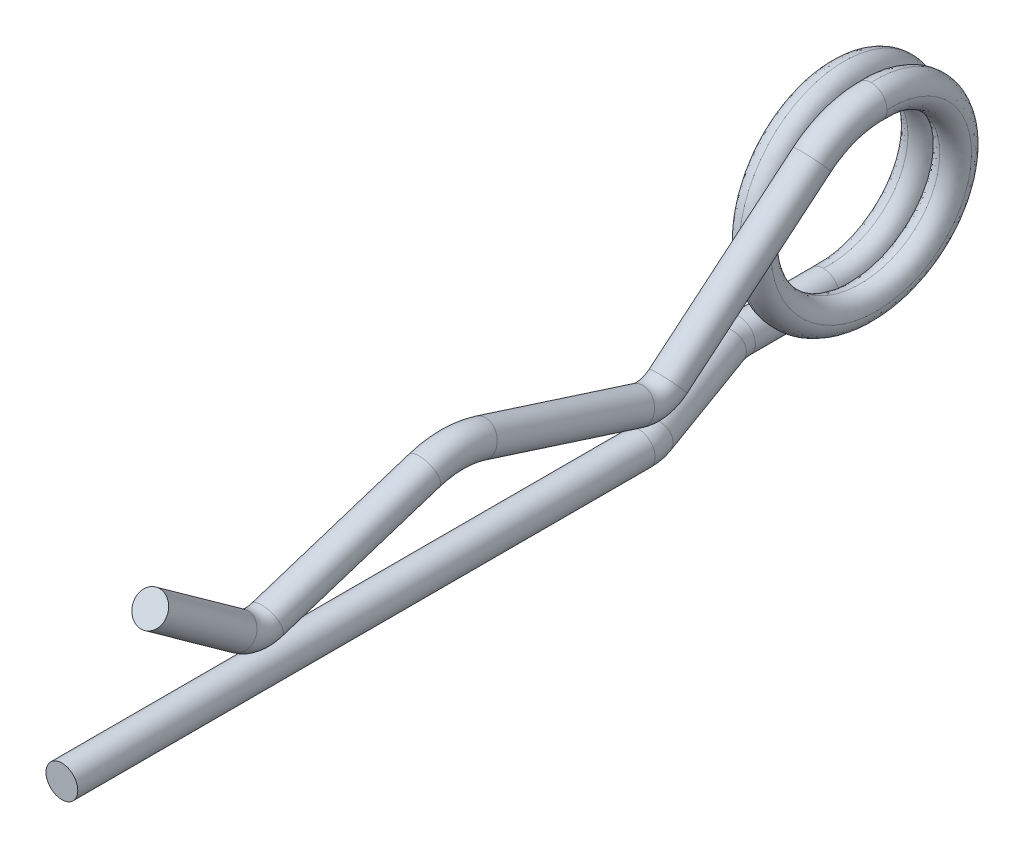
SolidWorks part; units mm, degrees
ref_plane "Front" through (0, 0, 0) normal (0, 0, 1) x (1, 0, 0)
ref_plane "Top" through (0, 0, 0) normal (0, 1, 0) x (1, 0, 0)
ref_plane "Right" through (0, 0, 0) normal (1, 0, 0) x (0, 0, -1)
sketch "Sketch1" plane through (0, 0, 0) normal (0, 0, 1) x (1, 0, 0)
  circle A0 centre (0, 0) radius 0.9906
  dimension "WireOD" = 1.9812
sketch "Sketch2" plane through (0, 0, 0) normal (0, 1, 0) x (1, 0, 0)
  line L0 (0, 0) -> (0, 35.9642)
  line L1 (-0.1792, 36.9807) -> (-2.7926, 44.1608)
  line L2 (-2.9718, 45.1772) -> (-2.9718, 50.4063)
  line L3 (-2.9718, 50.4063) -> (0, 50.4063) construction
  line L4 (0, 45.6438) -> (0, 55.1688) construction
  line L5 (0, 55.1688) -> (0, 57.15) construction
  line L6 (0, 45.6438) -> (0, 43.6626) construction
  line L7 (0, 44.6532) -> (-2.9718, 44.6532) construction
  arc A0 (-2.7926, 44.1608) -> (-2.9718, 45.1772) centre (0, 45.1772) cw
  arc A1 (0, 35.9642) -> (-0.1792, 36.9807) centre (-2.9718, 35.9642) ccw
  point P16 (0, 36.4882)
  dimension "D5" = 2.9718
  dimension "D1" = 2.9718
  dimension "EyeID" = 9.525
  dimension "D2" = 1.9812
  dimension "Length" = 57.15
  dimension "D4" = 20
sketch "Sketch3" plane through (0, 0, 0) normal (1, 0, 0) x (0, 0, -1)
  line L1 (50.4063, 0) -> (50.4063, 5.7531) construction
  line L2 (45.6438, 0) -> (55.1688, 0) construction
  line L3 (44.6532, 0) -> (44.6532, 5.7531) construction
  line L4 (45.6438, 0) -> (43.6626, 0) construction
  line L5 (50.4063, 5.7531) -> (44.6532, 5.7531) construction
  circle A0 centre (50.4063, 5.7531) radius 5.7531
curve "Helix/Spiral1" pitch 1.9812 height 2.9718 radius 5.7531 centre (0, 5.7531, -50.4063) axis (-1, 0, 0) start towards (0, 1, 0)
sketch "Sketch4" plane through (0, 0, 0) normal (1, 0, 0) x (0, 0, -1)
  line L0 (50.4063, 5.7531) -> (50.4063, 11.5062) construction
  line L1 (46.7215, 10.1713) -> (37.7572, 2.6949)
  line L2 (36.4882, 0) -> (36.4882, 2.2352) construction
  line L3 (12.1627, 0) -> (12.1627, 2.2352) construction
  line L4 (0, 0) -> (35.9642, 0) construction
  line L5 (36.4882, 0) -> (24.3255, 0) construction
  line L6 (11.0074, 2.607) -> (5.5037, 6.5578)
  line L7 (4.926, 5.7531) -> (6.0814, 7.3625) construction
  line L8 (45.6438, 0) -> (43.6626, 0) construction
  line L9 (44.6532, 5.7531) -> (4.926, 5.7531) construction
  line L10 (12.1627, 1.1176) -> (36.4882, 1.1176) construction
  line L11 (24.3255, 0) -> (24.3255, 5.7531) construction
  line L12 (35.8823, 2.3301) -> (26.0851, 5.4774)
  line L13 (22.5659, 5.4774) -> (12.7687, 2.3301)
  line L14 (6.0814, 0) -> (6.0814, 7.3625) construction
  line L15 (24.3255, 0) -> (12.1627, 0) construction
  line L16 (12.1627, 0) -> (0, 0) construction
  line L17 (0, 0.9906) -> (0, -0.9906) construction
  line L18 (0, 0) -> (0, 11.5062) construction
  line L19 (0, 11.5062) -> (57.15, 11.5062) construction
  line L20 (57.15, 11.5062) -> (57.15, 0) construction
  line L21 (55.1688, 0) -> (57.15, 0) construction
  line L22 (45.6438, 0) -> (45.6438, 5.7531) construction
  line L23 (45.6438, 5.7531) -> (55.1688, 5.7531) construction
  line L24 (24.3255, 4.6355) -> (24.3255, 6.8707) construction
  circle A0 centre (50.4063, 5.7531) radius 5.7531 construction
  arc A1 (50.4063, 11.5062) -> (46.7215, 10.1713) centre (50.4063, 5.7531) ccw
  arc A2 (35.8823, 2.3301) -> (37.7572, 2.6949) centre (36.4882, 4.2164) ccw
  arc A3 (11.0074, 2.607) -> (12.7687, 2.3301) centre (12.1627, 4.2164) ccw
  arc A4 (26.0851, 5.4774) -> (22.5659, 5.4774) centre (24.3255, 0) ccw
  circle A5 centre (24.3255, 2.8766) radius 1.759 construction
  point P46 (24.3255, 5.7531)
  point P50 (24.3255, 2.8766)
  dimension "D2" = 3.9624
  dimension "D1" = 2.2352
sweep "Sweep1" add profiles "Sketch1" path "Sketch2"
sketch "Sketch5" plane through (0, 0, -50.4063) normal (0, 0, -1) x (-1, 0, 0)
  circle A1 centre (2.9718, 0) radius 0.9906
  circle A2 centre (2.9718, 0) radius 0.9906
  dimension "D1" = 0
sweep "Sweep2" add profiles "Sketch5" path "Helix/Spiral1"
sketch "Sketch6" plane through (0, 0, -50.4063) normal (0, 0, 1) x (1, 0, 0)
  arc A4 (0.9906, 11.5062) -> (0, 12.4968) centre (0, 11.5062) ccw
  arc A5 (0, 12.4968) -> (-0.9906, 11.5062) centre (0, 11.5062) ccw
  arc A6 (-0.9906, 11.5062) -> (0, 10.5156) centre (0, 11.5062) ccw
  arc A7 (0, 10.5156) -> (0.9906, 11.5062) centre (0, 11.5062) ccw
  arc A8 (0.9906, 11.5062) -> (0, 12.4968) centre (0, 11.5062) ccw
  arc A9 (0, 12.4968) -> (-0.9906, 11.5062) centre (0, 11.5062) ccw
  arc A10 (-0.9906, 11.5062) -> (0, 10.5156) centre (0, 11.5062) ccw
  arc A11 (0, 10.5156) -> (0.9906, 11.5062) centre (0, 11.5062) ccw
  dimension "D1" = 0
sweep "Sweep3" add profiles "Sketch6" path "Sketch4"
ref_axis "Center Axis 1" through (0, 2.8766, -24.3255) along (1, 0, 0)
equation "\"D1@Sketch2\" =\"WireOD@Sketch1\"*1.5"
equation "\"D2@Sketch2\" = \"WireOD@Sketch1\""
equation "\"D5@Sketch2\" = \"WireOD@Sketch1\"*1.5"
equation "\"D4@Helix/Spiral1\" = \"WireOD@Sketch1\""
equation "\"D2@Sketch4\" = \"WireOD@Sketch1\"*2"
equation "\"D1@Sketch4\" = \"WireOD@Sketch1\"+.01"
